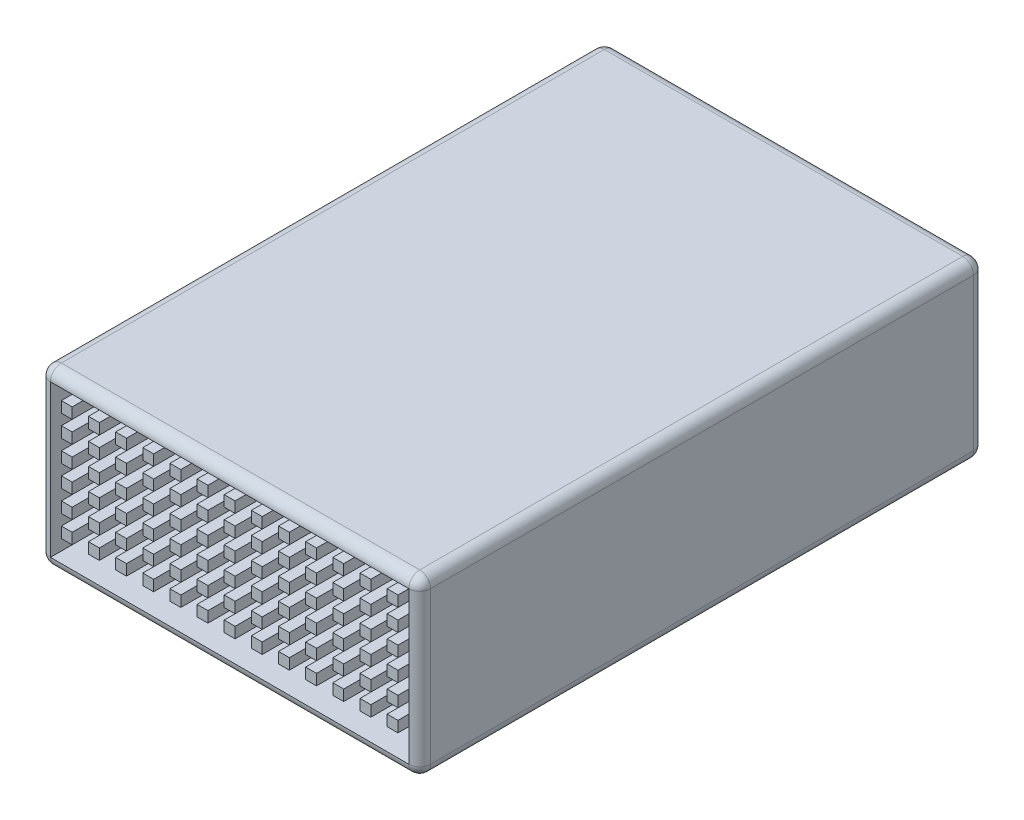
SolidWorks part; units mm, degrees
ref_plane "Front Plane" through (0, 0, 0) normal (0, 0, 1) x (1, 0, 0)
ref_plane "Top Plane" through (0, 0, 0) normal (0, 1, 0) x (1, 0, 0)
ref_plane "Right Plane" through (0, 0, 0) normal (1, 0, 0) x (0, 0, -1)
sketch "Sketch1" plane through (0, 0, 0) normal (0, 1, 0) x (1, 0, 0)
  line L1 (17.5, 26) -> (-17.5, 26)
  line L2 (17.5, 26) -> (17.5, -26)
  line L3 (17.5, -26) -> (-17.5, -26)
  line L4 (-17.5, 26) -> (-17.5, -26)
  line L5 (0, -26) -> (0, 26) construction
  line L6 (17.5, 0) -> (-17.5, 0) construction
  point P0 (0, 0)
  dimension "D1" = 35
  dimension "D2" = 52
extrude "Boss-Extrude1" add sketch "Sketch1" along normal blind 16
sketch "Sketch2" plane through (0, 0, 26) normal (0, 0, 1) x (1, 0, 0)
  line L4 (-13, 14) -> (-13, 13)
  line L5 (-15.5, 14) -> (-14.5, 14)
  line L6 (-15.5, 14) -> (-15.5, 13)
  line L7 (-15.5, 13) -> (-14.5, 13)
  line L8 (-16.5, 1) -> (16.5, 1)
  line L9 (16.5, 1) -> (16.5, 15)
  line L10 (16.5, 15) -> (-16.5, 15)
  line L11 (-16.5, 15) -> (-16.5, 1)
  line L12 (-16.5, 1) -> (16.5, 1)
  line L13 (16.5, 1) -> (16.5, 15)
  line L14 (16.5, 15) -> (-16.5, 15)
  line L15 (-16.5, 15) -> (-16.5, 1)
  line L16 (-14.5, 14) -> (-14.5, 13)
  line L17 (-15, 13) -> (-15, 14) construction
  line L18 (-15.5, 13.5) -> (-14.5, 13.5) construction
  line L19 (-13, 14) -> (-12, 14)
  line L20 (-12, 14) -> (-12, 13)
  line L21 (-13, 13) -> (-12, 13)
  line L22 (-10.5, 14) -> (-10.5, 13)
  line L23 (-10.5, 14) -> (-9.5, 14)
  line L24 (-9.5, 14) -> (-9.5, 13)
  line L25 (-10.5, 13) -> (-9.5, 13)
  line L26 (-8, 14) -> (-8, 13)
  line L27 (-8, 14) -> (-7, 14)
  line L28 (-7, 14) -> (-7, 13)
  line L29 (-8, 13) -> (-7, 13)
  line L30 (-5.5, 14) -> (-5.5, 13)
  line L31 (-5.5, 14) -> (-4.5, 14)
  line L32 (-4.5, 14) -> (-4.5, 13)
  line L33 (-5.5, 13) -> (-4.5, 13)
  line L34 (-3, 14) -> (-3, 13)
  line L35 (-3, 14) -> (-2, 14)
  line L36 (-2, 14) -> (-2, 13)
  line L37 (-3, 13) -> (-2, 13)
  line L38 (-0.5, 14) -> (-0.5, 13)
  line L39 (-0.5, 14) -> (0.5, 14)
  line L40 (0.5, 14) -> (0.5, 13)
  line L41 (-0.5, 13) -> (0.5, 13)
  line L42 (2, 14) -> (2, 13)
  line L43 (2, 14) -> (3, 14)
  line L44 (3, 14) -> (3, 13)
  line L45 (2, 13) -> (3, 13)
  line L46 (4.5, 14) -> (4.5, 13)
  line L47 (4.5, 14) -> (5.5, 14)
  line L48 (5.5, 14) -> (5.5, 13)
  line L49 (4.5, 13) -> (5.5, 13)
  line L50 (7, 14) -> (7, 13)
  line L51 (7, 14) -> (8, 14)
  line L52 (8, 14) -> (8, 13)
  line L53 (7, 13) -> (8, 13)
  line L54 (9.5, 14) -> (9.5, 13)
  line L55 (9.5, 14) -> (10.5, 14)
  line L56 (10.5, 14) -> (10.5, 13)
  line L57 (9.5, 13) -> (10.5, 13)
  line L58 (12, 14) -> (12, 13)
  line L59 (12, 14) -> (13, 14)
  line L60 (13, 14) -> (13, 13)
  line L61 (12, 13) -> (13, 13)
  line L62 (14.5, 14) -> (14.5, 13)
  line L63 (14.5, 14) -> (15.5, 14)
  line L64 (15.5, 14) -> (15.5, 13)
  line L65 (14.5, 13) -> (15.5, 13)
  line L66 (14.5, 12) -> (14.5, 11)
  line L67 (14.5, 11) -> (15.5, 11)
  line L68 (15.5, 12) -> (15.5, 11)
  line L69 (14.5, 12) -> (15.5, 12)
  line L70 (12, 12) -> (12, 11)
  line L71 (12, 11) -> (13, 11)
  line L72 (13, 12) -> (13, 11)
  line L73 (12, 12) -> (13, 12)
  line L74 (9.5, 12) -> (9.5, 11)
  line L75 (9.5, 11) -> (10.5, 11)
  line L76 (10.5, 12) -> (10.5, 11)
  line L77 (9.5, 12) -> (10.5, 12)
  line L78 (7, 12) -> (7, 11)
  line L79 (7, 11) -> (8, 11)
  line L80 (8, 12) -> (8, 11)
  line L81 (7, 12) -> (8, 12)
  line L82 (4.5, 12) -> (4.5, 11)
  line L83 (4.5, 11) -> (5.5, 11)
  line L84 (5.5, 12) -> (5.5, 11)
  line L85 (4.5, 12) -> (5.5, 12)
  line L86 (2, 12) -> (2, 11)
  line L87 (2, 11) -> (3, 11)
  line L88 (3, 12) -> (3, 11)
  line L89 (2, 12) -> (3, 12)
  line L90 (-5.5, 12) -> (-5.5, 11)
  line L91 (-5.5, 11) -> (-4.5, 11)
  line L92 (-4.5, 12) -> (-4.5, 11)
  line L93 (-5.5, 12) -> (-4.5, 12)
  line L94 (-8, 12) -> (-8, 11)
  line L95 (-8, 11) -> (-7, 11)
  line L96 (-7, 12) -> (-7, 11)
  line L97 (-8, 12) -> (-7, 12)
  line L98 (-10.5, 12) -> (-10.5, 11)
  line L99 (-10.5, 11) -> (-9.5, 11)
  line L100 (-9.5, 12) -> (-9.5, 11)
  line L101 (-10.5, 12) -> (-9.5, 12)
  line L102 (-13, 12) -> (-13, 11)
  line L103 (-13, 11) -> (-12, 11)
  line L104 (-12, 12) -> (-12, 11)
  line L105 (-13, 12) -> (-12, 12)
  line L106 (-0.5, 12) -> (-0.5, 11)
  line L107 (-0.5, 11) -> (0.5, 11)
  line L108 (0.5, 12) -> (0.5, 11)
  line L109 (-0.5, 12) -> (0.5, 12)
  line L110 (-3, 12) -> (-3, 11)
  line L111 (-3, 11) -> (-2, 11)
  line L112 (-2, 12) -> (-2, 11)
  line L113 (-3, 12) -> (-2, 12)
  line L114 (-15.5, 12) -> (-15.5, 11)
  line L115 (-15.5, 12) -> (-14.5, 12)
  line L116 (-14.5, 12) -> (-14.5, 11)
  line L117 (-15.5, 11) -> (-14.5, 11)
  line L118 (14.5, 10) -> (14.5, 9)
  line L119 (14.5, 9) -> (15.5, 9)
  line L120 (15.5, 10) -> (15.5, 9)
  line L121 (14.5, 10) -> (15.5, 10)
  line L122 (12, 10) -> (12, 9)
  line L123 (12, 9) -> (13, 9)
  line L124 (13, 10) -> (13, 9)
  line L125 (12, 10) -> (13, 10)
  line L126 (9.5, 10) -> (9.5, 9)
  line L127 (9.5, 9) -> (10.5, 9)
  line L128 (10.5, 10) -> (10.5, 9)
  line L129 (9.5, 10) -> (10.5, 10)
  line L130 (7, 10) -> (7, 9)
  line L131 (7, 9) -> (8, 9)
  line L132 (8, 10) -> (8, 9)
  line L133 (7, 10) -> (8, 10)
  line L134 (4.5, 10) -> (4.5, 9)
  line L135 (4.5, 9) -> (5.5, 9)
  line L136 (5.5, 10) -> (5.5, 9)
  line L137 (4.5, 10) -> (5.5, 10)
  line L138 (2, 10) -> (2, 9)
  line L139 (2, 9) -> (3, 9)
  line L140 (3, 10) -> (3, 9)
  line L141 (2, 10) -> (3, 10)
  line L142 (-5.5, 10) -> (-5.5, 9)
  line L143 (-5.5, 9) -> (-4.5, 9)
  line L144 (-4.5, 10) -> (-4.5, 9)
  line L145 (-5.5, 10) -> (-4.5, 10)
  line L146 (-8, 10) -> (-8, 9)
  line L147 (-8, 9) -> (-7, 9)
  line L148 (-7, 10) -> (-7, 9)
  line L149 (-8, 10) -> (-7, 10)
  line L150 (-10.5, 10) -> (-10.5, 9)
  line L151 (-10.5, 9) -> (-9.5, 9)
  line L152 (-9.5, 10) -> (-9.5, 9)
  line L153 (-10.5, 10) -> (-9.5, 10)
  line L154 (-13, 10) -> (-13, 9)
  line L155 (-13, 9) -> (-12, 9)
  line L156 (-12, 10) -> (-12, 9)
  line L157 (-13, 10) -> (-12, 10)
  line L158 (-0.5, 10) -> (-0.5, 9)
  line L159 (-0.5, 9) -> (0.5, 9)
  line L160 (0.5, 10) -> (0.5, 9)
  line L161 (-0.5, 10) -> (0.5, 10)
  line L162 (-3, 10) -> (-3, 9)
  line L163 (-3, 9) -> (-2, 9)
  line L164 (-2, 10) -> (-2, 9)
  line L165 (-3, 10) -> (-2, 10)
  line L166 (-15.5, 10) -> (-15.5, 9)
  line L167 (-15.5, 10) -> (-14.5, 10)
  line L168 (-14.5, 10) -> (-14.5, 9)
  line L169 (-15.5, 9) -> (-14.5, 9)
  line L170 (14.5, 8) -> (14.5, 7)
  line L171 (14.5, 7) -> (15.5, 7)
  line L172 (15.5, 8) -> (15.5, 7)
  line L173 (14.5, 8) -> (15.5, 8)
  line L174 (12, 8) -> (12, 7)
  line L175 (12, 7) -> (13, 7)
  line L176 (13, 8) -> (13, 7)
  line L177 (12, 8) -> (13, 8)
  line L178 (9.5, 8) -> (9.5, 7)
  line L179 (9.5, 7) -> (10.5, 7)
  line L180 (10.5, 8) -> (10.5, 7)
  line L181 (9.5, 8) -> (10.5, 8)
  line L182 (7, 8) -> (7, 7)
  line L183 (7, 7) -> (8, 7)
  line L184 (8, 8) -> (8, 7)
  line L185 (7, 8) -> (8, 8)
  line L186 (4.5, 8) -> (4.5, 7)
  line L187 (4.5, 7) -> (5.5, 7)
  line L188 (5.5, 8) -> (5.5, 7)
  line L189 (4.5, 8) -> (5.5, 8)
  line L190 (2, 8) -> (2, 7)
  line L191 (2, 7) -> (3, 7)
  line L192 (3, 8) -> (3, 7)
  line L193 (2, 8) -> (3, 8)
  line L194 (-5.5, 8) -> (-5.5, 7)
  line L195 (-5.5, 7) -> (-4.5, 7)
  line L196 (-4.5, 8) -> (-4.5, 7)
  line L197 (-5.5, 8) -> (-4.5, 8)
  line L198 (-8, 8) -> (-8, 7)
  line L199 (-8, 7) -> (-7, 7)
  line L200 (-7, 8) -> (-7, 7)
  line L201 (-8, 8) -> (-7, 8)
  line L202 (-10.5, 8) -> (-10.5, 7)
  line L203 (-10.5, 7) -> (-9.5, 7)
  line L204 (-9.5, 8) -> (-9.5, 7)
  line L205 (-10.5, 8) -> (-9.5, 8)
  line L206 (-13, 8) -> (-13, 7)
  line L207 (-13, 7) -> (-12, 7)
  line L208 (-12, 8) -> (-12, 7)
  line L209 (-13, 8) -> (-12, 8)
  line L210 (-0.5, 8) -> (-0.5, 7)
  line L211 (-0.5, 7) -> (0.5, 7)
  line L212 (0.5, 8) -> (0.5, 7)
  line L213 (-0.5, 8) -> (0.5, 8)
  line L214 (-3, 8) -> (-3, 7)
  line L215 (-3, 7) -> (-2, 7)
  line L216 (-2, 8) -> (-2, 7)
  line L217 (-3, 8) -> (-2, 8)
  line L218 (-15.5, 8) -> (-15.5, 7)
  line L219 (-15.5, 8) -> (-14.5, 8)
  line L220 (-14.5, 8) -> (-14.5, 7)
  line L221 (-15.5, 7) -> (-14.5, 7)
  line L222 (14.5, 6) -> (14.5, 5)
  line L223 (14.5, 5) -> (15.5, 5)
  line L224 (15.5, 6) -> (15.5, 5)
  line L225 (14.5, 6) -> (15.5, 6)
  line L226 (12, 6) -> (12, 5)
  line L227 (12, 5) -> (13, 5)
  line L228 (13, 6) -> (13, 5)
  line L229 (12, 6) -> (13, 6)
  line L230 (9.5, 6) -> (9.5, 5)
  line L231 (9.5, 5) -> (10.5, 5)
  line L232 (10.5, 6) -> (10.5, 5)
  line L233 (9.5, 6) -> (10.5, 6)
  line L234 (7, 6) -> (7, 5)
  line L235 (7, 5) -> (8, 5)
  line L236 (8, 6) -> (8, 5)
  line L237 (7, 6) -> (8, 6)
  line L238 (4.5, 6) -> (4.5, 5)
  line L239 (4.5, 5) -> (5.5, 5)
  line L240 (5.5, 6) -> (5.5, 5)
  line L241 (4.5, 6) -> (5.5, 6)
  line L242 (2, 6) -> (2, 5)
  line L243 (2, 5) -> (3, 5)
  line L244 (3, 6) -> (3, 5)
  line L245 (2, 6) -> (3, 6)
  line L246 (-5.5, 6) -> (-5.5, 5)
  line L247 (-5.5, 5) -> (-4.5, 5)
  line L248 (-4.5, 6) -> (-4.5, 5)
  line L249 (-5.5, 6) -> (-4.5, 6)
  line L250 (-8, 6) -> (-8, 5)
  line L251 (-8, 5) -> (-7, 5)
  line L252 (-7, 6) -> (-7, 5)
  line L253 (-8, 6) -> (-7, 6)
  line L254 (-10.5, 6) -> (-10.5, 5)
  line L255 (-10.5, 5) -> (-9.5, 5)
  line L256 (-9.5, 6) -> (-9.5, 5)
  line L257 (-10.5, 6) -> (-9.5, 6)
  line L258 (-13, 6) -> (-13, 5)
  line L259 (-13, 5) -> (-12, 5)
  line L260 (-12, 6) -> (-12, 5)
  line L261 (-13, 6) -> (-12, 6)
  line L262 (-0.5, 6) -> (-0.5, 5)
  line L263 (-0.5, 5) -> (0.5, 5)
  line L264 (0.5, 6) -> (0.5, 5)
  line L265 (-0.5, 6) -> (0.5, 6)
  line L266 (-3, 6) -> (-3, 5)
  line L267 (-3, 5) -> (-2, 5)
  line L268 (-2, 6) -> (-2, 5)
  line L269 (-3, 6) -> (-2, 6)
  line L270 (-15.5, 6) -> (-15.5, 5)
  line L271 (-15.5, 6) -> (-14.5, 6)
  line L272 (-14.5, 6) -> (-14.5, 5)
  line L273 (-15.5, 5) -> (-14.5, 5)
  line L274 (14.5, 4) -> (14.5, 3)
  line L275 (14.5, 3) -> (15.5, 3)
  line L276 (15.5, 4) -> (15.5, 3)
  line L277 (14.5, 4) -> (15.5, 4)
  line L278 (12, 4) -> (12, 3)
  line L279 (12, 3) -> (13, 3)
  line L280 (13, 4) -> (13, 3)
  line L281 (12, 4) -> (13, 4)
  line L282 (9.5, 4) -> (9.5, 3)
  line L283 (9.5, 3) -> (10.5, 3)
  line L284 (10.5, 4) -> (10.5, 3)
  line L285 (9.5, 4) -> (10.5, 4)
  line L286 (7, 4) -> (7, 3)
  line L287 (7, 3) -> (8, 3)
  line L288 (8, 4) -> (8, 3)
  line L289 (7, 4) -> (8, 4)
  line L290 (4.5, 4) -> (4.5, 3)
  line L291 (4.5, 3) -> (5.5, 3)
  line L292 (5.5, 4) -> (5.5, 3)
  line L293 (4.5, 4) -> (5.5, 4)
  line L294 (2, 4) -> (2, 3)
  line L295 (2, 3) -> (3, 3)
  line L296 (3, 4) -> (3, 3)
  line L297 (2, 4) -> (3, 4)
  line L298 (-5.5, 4) -> (-5.5, 3)
  line L299 (-5.5, 3) -> (-4.5, 3)
  line L300 (-4.5, 4) -> (-4.5, 3)
  line L301 (-5.5, 4) -> (-4.5, 4)
  line L302 (-8, 4) -> (-8, 3)
  line L303 (-8, 3) -> (-7, 3)
  line L304 (-7, 4) -> (-7, 3)
  line L305 (-8, 4) -> (-7, 4)
  line L306 (-10.5, 4) -> (-10.5, 3)
  line L307 (-10.5, 3) -> (-9.5, 3)
  line L308 (-9.5, 4) -> (-9.5, 3)
  line L309 (-10.5, 4) -> (-9.5, 4)
  line L310 (-13, 4) -> (-13, 3)
  line L311 (-13, 3) -> (-12, 3)
  line L312 (-12, 4) -> (-12, 3)
  line L313 (-13, 4) -> (-12, 4)
  line L314 (-0.5, 4) -> (-0.5, 3)
  line L315 (-0.5, 3) -> (0.5, 3)
  line L316 (0.5, 4) -> (0.5, 3)
  line L317 (-0.5, 4) -> (0.5, 4)
  line L318 (-3, 4) -> (-3, 3)
  line L319 (-3, 3) -> (-2, 3)
  line L320 (-2, 4) -> (-2, 3)
  line L321 (-3, 4) -> (-2, 4)
  line L322 (-15.5, 4) -> (-15.5, 3)
  line L323 (-15.5, 4) -> (-14.5, 4)
  line L324 (-14.5, 4) -> (-14.5, 3)
  line L325 (-15.5, 3) -> (-14.5, 3)
  point P0 (-15, 13.5)
  dimension "D2" = 1
  dimension "D3" = 1
  dimension "D4" = 1
  dimension "D1" = 1
  dimension "D5" = 13
  dimension "D6" = 6
extrude "Cut-Extrude1" cut sketch "Sketch2" against normal blind 15
fillet "Fillet1" radius 1 12 edges at (0, 16, 26) (-17.5, 16, 0) (-17.5, 8, 26) (0, 0, 26) (-17.5, 0, 0) (0, 16, -26) (-17.5, 8, -26) (0, 0, -26) (17.5, 8, 26) (17.5, 16, 0) (17.5, 8, -26) (17.5, 0, 0)
